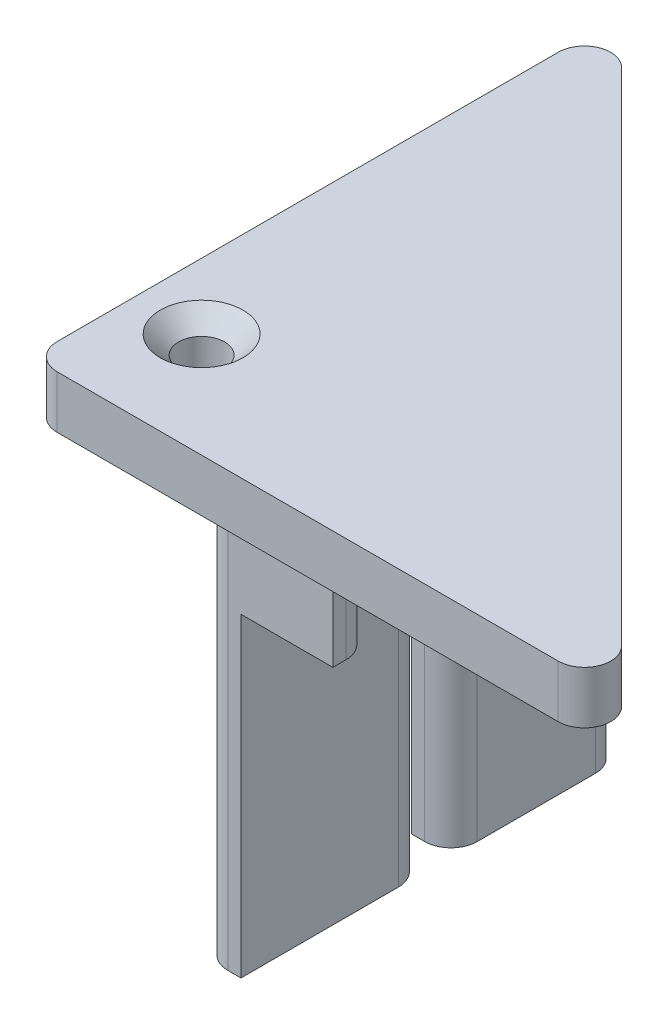
SolidWorks part; units mm, degrees
ref_plane "Płaszczyzna przednia" through (0, 0, 0) normal (0, 0, 1) x (1, 0, 0)
ref_plane "Płaszczyzna górna" through (0, 0, 0) normal (0, 1, 0) x (1, 0, 0)
ref_plane "Płaszczyzna prawa" through (0, 0, 0) normal (1, 0, 0) x (0, 0, -1)
sketch "Sketch1" plane through (0, 0, 0) normal (0, 1, 0) x (1, 0, 0)
  line L0 (-22.8113, 22.8113) -> (22.1887, -22.1887)
  line L2 (-22.8113, 22.8113) -> (-22.8113, -22.1887)
  line L3 (-22.8113, -22.1887) -> (22.1887, -22.1887)
  line L5 (-22.8113, 22.8113) -> (22.1887, -22.1887) construction
  line L6 (-22.8113, -22.1887) -> (0, 0) construction
  circle A0 centre (-17.8113, -14.1887) radius 1.75
  point P0 (0, 0)
  dimension "D3" = 8
  dimension "D5" = 3.5
  dimension "D1" = 45
  dimension "D2" = 45
  dimension "D4" = 5
extrude "Boss-Extrude1" add sketch "Sketch1" along normal blind 4
sketch "Sketch2" plane through (0, 4, 0) normal (0, 1, 0) x (1, 0, 0)
  point P0 (-17.8113, -14.1887)
hole_wizard "CSK for M3 Countersunk Flat Head Screw1" positions "Sketch2" profile "Sketch3" countersink size "M3" standard "ISO" end condition through all
sketch "Sketch3" plane through (-17.8113, 4, 14.1887) normal (1, 0, 0) x (0, 0, 1)
  line L0 (0, 0) -> (0, 4)
  line L1 (0, 4) -> (1.6, 4)
  line L2 (1.6, 4) -> (1.6, 1.55)
  line L3 (1.6, 1.55) -> (3.15, 0)
  line L5 (3.15, 0) -> (0, 0)
  line L6 (-1.6, 1.55) -> (-3.15, 0) construction
  line L11 (0, -6.35) -> (0, 107.95) construction
  dimension "Thru Hole Dia." = 3.2
  dimension "Thru Hole Depth" = 4
  dimension "Near C'Sink Dia." = 6.3
  dimension "Near C'Sink Angle" = 90
fillet "Fillet1" radius 2 3 edges at (-22.8113, 2, 22.1887) (22.1887, 2, 22.1887) (-22.8113, 2, -22.8113)
sketch "Sketch5" plane through (0, 0, 0) normal (0, -1, 0) x (1, 0, 0)
  line L0 (-12.8113, 5.5582) -> (-12.8113, -12.8113)
  line L1 (18.7745, 18.7745) -> (-19.3971, -19.3971) construction
  line L2 (-22.8113, -17.9829) -> (-22.8113, 20.1887) construction
  line L3 (-9.8113, -9.8113) -> (-12.8113, -12.8113)
  line L5 (-12.8113, -12.8113) -> (-12.8113, 19.1887)
  line L6 (-12.8113, 19.1887) -> (-9.8113, 19.1887)
  line L7 (-9.8113, -9.8113) -> (-9.8113, 19.1887)
  line L8 (-20.8113, 22.1887) -> (17.3603, 22.1887) construction
  line L9 (-12.8113, 19.1887) -> (-12.8113, 5.5582)
  line L10 (-12.8113, 5.1887) -> (-9.8113, 5.1887)
  line L11 (-12.8113, 3.1887) -> (-9.8113, 3.1887)
  line L12 (-9.8113, -9.8113) -> (-12.8113, -12.8113)
  line L13 (-12.8113, -12.8113) -> (-9.8113, -9.8113)
  line L14 (-12.8113, -12.8113) -> (-9.8113, -9.8113)
  line L15 (-9.8113, -9.8113) -> (-12.8113, -9.8113)
  dimension "D1" = 10
  dimension "D2" = 3
  dimension "D3" = 3
  dimension "D4" = 17
  dimension "D5" = 2
extrude "Boss-Extrude2" add sketch "Sketch5" along normal blind 32 contours L0 L10 L7 L6 L5 | L15 L7 L11 L0 region at (-11.3113, 0, 12.1887) region at (-11.3113, 0, -3.3113)
sketch "Sketch6" plane through (0, 0, 0) normal (0, -1, 0) x (1, 0, 0)
  line L1 (-9.8113, 19.1887) -> (-2.8113, 19.1887)
  line L2 (-9.8113, 19.1887) -> (-9.8113, 16.1887)
  line L3 (-9.8113, 16.1887) -> (-2.8113, 16.1887)
  line L4 (-2.8113, 19.1887) -> (-2.8113, 16.1887)
  line L5 (-9.8113, 19.1887) -> (-2.8113, 16.1887) construction
  line L6 (-9.8113, 16.1887) -> (-2.8113, 19.1887) construction
  point P4 (-6.3113, 17.6887)
  dimension "D1" = 3
  dimension "D2" = 7
extrude "Boss-Extrude3" add sketch "Sketch6" along normal blind 8
fillet "Fillet2" radius 2 5 edges at (-12.8113, -16, 19.1887) (-9.8113, -16, -9.8113) (-2.8113, -4, 16.1887) (-9.8113, -16, 3.1887) (-9.8113, -16, 5.1887)
